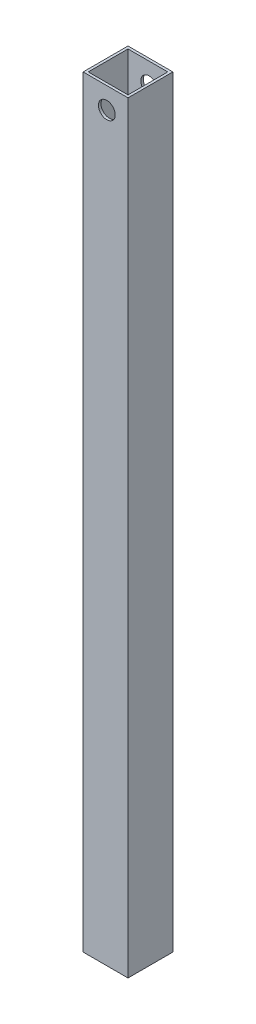
SolidWorks part; units mm, degrees
material "6061 Alloy"
ref_plane "Front Plane" through (0, 0, 0) normal (0, 0, 1) x (1, 0, 0)
ref_plane "Top Plane" through (0, 0, 0) normal (0, 1, 0) x (1, 0, 0)
ref_plane "Right Plane" through (0, 0, 0) normal (1, 0, 0) x (0, 0, -1)
sketch "Sketch1" plane through (0, 0, 0) normal (0, 1, 0) x (1, 0, 0)
  line L9 (12.7, -12.7) -> (-12.7, -12.7)
  line L10 (12.7, -12.7) -> (12.7, 12.7)
  line L11 (12.7, 12.7) -> (-12.7, 12.7)
  line L12 (-12.7, -12.7) -> (-12.7, 12.7)
  line L13 (12.7, -12.7) -> (-12.7, 12.7) construction
  line L14 (12.7, 12.7) -> (-12.7, -12.7) construction
  point P0 (0, 0)
  dimension "D1" = 25.4
extrude "Extrude-Thin1" add sketch "Sketch1" along normal blind 457.2 thin thin type mid plane wall 1.524
sketch "Sketch2" plane through (0, 0, 13.462) normal (0, 0, 1) x (1, 0, 0)
  line L0 (-13.462, 457.2) -> (13.462, 457.2) construction
  line L1 (13.462, 457.2) -> (13.462, 0) construction
  circle A0 centre (0.762, 444.5) radius 5.0419
  dimension "D1" = 10.0838
  dimension "D2" = 12.7
  dimension "D3" = 12.7
extrude "Cut-Extrude1" cut sketch "Sketch2" against normal through all
